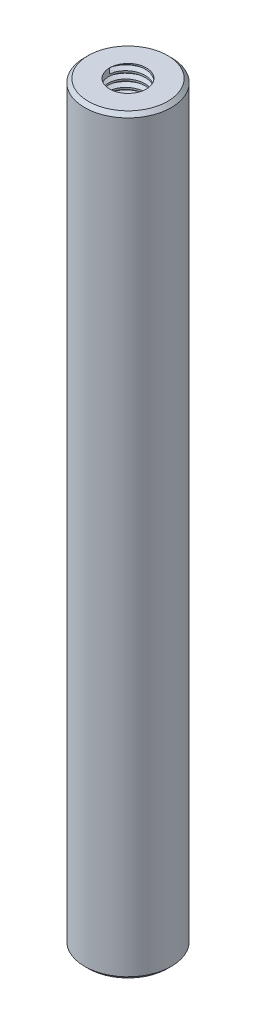
SolidWorks part; units mm, degrees
material "6061-T6 (SS)"
ref_plane "Alzado" through (0, 0, 0) normal (0, 0, 1) x (1, 0, 0)
ref_plane "Planta" through (0, 0, 0) normal (0, 1, 0) x (1, 0, 0)
ref_plane "Vista lateral" through (0, 0, 0) normal (1, 0, 0) x (0, 0, -1)
sketch "Croquis2" plane through (0, 0, 0) normal (0, 1, 0) x (1, 0, 0)
  circle A0 centre (0, 0) radius 4.7625
  dimension "D1" = 9.525
extrude "Saliente-Extruir1" add sketch "Croquis2" along normal mid plane 82.55
chamfer "Chaflán1" distance 0.3969 angle 45 2 edges at (0, -41.275, 4.7625) (0, 41.275, 4.7625)
sketch "Croquis3" plane through (0, 0, 0) normal (0, 1, 0) x (1, 0, 0)
  circle A0 centre (0, 0) radius 2.0193
  dimension "D1" = 4.0386
extrude "Tap Hole 1" cut sketch "Croquis3" against normal blind 19.05 from surface starting at face at (0, 41.275, 4.3656)
extrude "Tap Hole 2" cut sketch "Croquis3<2>" along normal blind 19.05 from surface starting at face at (0, -41.275, 4.3656)
sketch "Croquis3<2>" plane through (0, 0, 0) normal (0, 1, 0) x (1, 0, 0) same geometry as "Croquis3"
sketch "Croquis4" plane through (0, 0, 0) normal (0, 1, 0) x (1, 0, 0)
  circle A0 centre (0, 0) radius 2.4892
  dimension "D1" = 4.9784
extrude "Clearance Hole" [suppressed] cut sketch "Croquis4" against normal through all both and the other way through all
thread "Rosca1" pitch 0.7937 method cut profile "Perfil de rosca1" start angle 0, offset 0, length 0, pitch 0.7937, diameter 4.0386
ref_plane "Plano1" through (-2.0193, 41.275, 0) normal (0, 0, 1) x (-1, 0, 0)
sketch "Perfil de rosca1" plane through (-2.0193, 41.275, 0) normal (0, 0, 1) x (-1, 0, 0)
  line L0 (0, 0) -> (0, 0.7937) construction
  line L1 (0, 0) -> (0.4296, 0.248)
  line L2 (0.4296, 0.248) -> (0.4296, 0.3473)
  line L3 (0.4296, 0.3473) -> (0, 0.5953)
  line L4 (0.4296, 0.2977) -> (0, 0.2977) construction
  line L11 (0, 0) -> (0, 0.5953)
  point P2 (0, 0)
  dimension "Pitch" = 0.7937
  dimension "Profile_Angle" = 60
  dimension "Profile_Land" = 0.0992
  dimension "Profile_Height" = 0.4296
thread "Rosca2" pitch 0.7937 method cut profile "Perfil de rosca2" start angle 0, offset 0, length 0, pitch 0.7937, diameter 4.0386
ref_plane "Plano2" through (2.0193, -41.275, 0) normal (0, 0, 1) x (1, 0, 0)
sketch "Perfil de rosca2" plane through (2.0193, -41.275, 0) normal (0, 0, 1) x (1, 0, 0)
  line L0 (0, 0) -> (0, 0.7937) construction
  line L1 (0, 0) -> (0.4296, 0.248)
  line L2 (0.4296, 0.248) -> (0.4296, 0.3473)
  line L3 (0.4296, 0.3473) -> (0, 0.5953)
  line L4 (0.4296, 0.2977) -> (0, 0.2977) construction
  line L11 (0, 0) -> (0, 0.5953)
  point P2 (0, 0)
  dimension "Pitch" = 0.7937
  dimension "Profile_Angle" = 60
  dimension "Profile_Land" = 0.0992
  dimension "Profile_Height" = 0.4296
equation "\"OD\"= 0.375pulgadas"
equation "\"Largo\"= 3.25pulgadas"
equation "\"Tap Hole\"= IIF ( \"OD\" = 0.375pulgadas , 0.1590pulgadas , 0.201pulgadas )"
equation "\"Spacer Hole\"= IIF ( \"OD\" = 0.375pulgadas , 0.196pulgadas , 0.257pulgadas )"
equation "\"D1@Croquis2\"=\"OD\""
equation "\"D1@Saliente-Extruir1\"=\"Largo\""
equation "\"D1@Croquis3\"=\"Tap Hole\""
equation "\"D1@Croquis4\"=\"Spacer Hole\""
